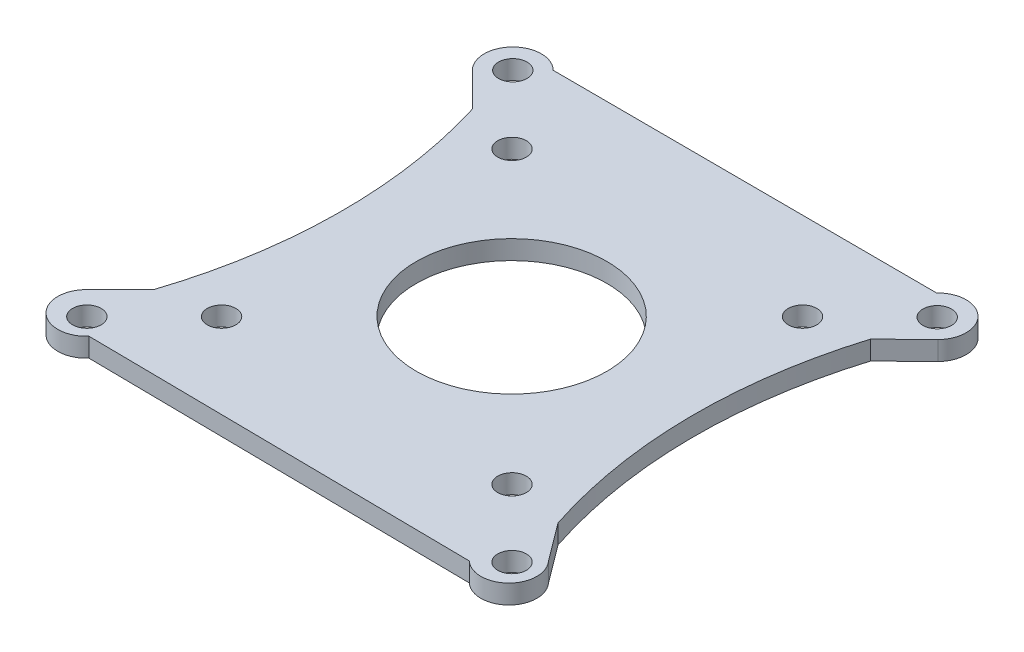
SolidWorks part; units mm, degrees
ref_plane "Front Plane" through (0, 0, 0) normal (0, 0, 1) x (1, 0, 0)
ref_plane "Top Plane" through (0, 0, 0) normal (0, 1, 0) x (1, 0, 0)
ref_plane "Right Plane" through (0, 0, 0) normal (1, 0, 0) x (0, 0, -1)
sketch "Sketch2" plane through (0, 0, 0) normal (0, 1, 0) x (1, 0, 0)
  line L0 (-78.5, 64.25) -> (-64.25, 78.5)
  line L1 (-15.25, 15.25) -> (15.25, 15.25)
  line L2 (-15.25, 15.25) -> (-15.25, -15.25)
  line L3 (-15.25, -15.25) -> (15.25, -15.25)
  line L4 (15.25, 15.25) -> (15.25, -15.25)
  line L5 (-15.25, 15.25) -> (15.25, -15.25) construction
  line L6 (-15.25, -15.25) -> (15.25, 15.25) construction
  line L7 (-78.5, 78.5) -> (78.5, 78.5)
  line L8 (-78.5, 78.5) -> (-78.5, -78.5)
  line L9 (-78.5, -78.5) -> (78.5, -78.5)
  line L10 (78.5, 78.5) -> (78.5, -78.5)
  line L11 (-78.5, 78.5) -> (78.5, -78.5) construction
  line L12 (-78.5, -78.5) -> (78.5, 78.5) construction
  line L13 (-78.5, 78.5) -> (-78.5457, 86.3999)
  line L19 (-78.5457, 64.1499) -> (-78.5457, 92.8503) construction
  line L21 (-78.5457, 86.3999) -> (-78.5457, 89.6265) construction
  line L22 (-79.8023, 86.3999) -> (-79.8023, 89.6265)
  line L23 (-77.2891, 86.3999) -> (-77.2891, 89.6265)
  line L24 (-78.5457, 70.6001) -> (-78.5457, 67.3735) construction
  line L25 (-79.8023, 70.6001) -> (-79.8023, 67.3735)
  line L26 (-77.2891, 70.6001) -> (-77.2891, 67.3735)
  line L27 (-70.6001, 78.5457) -> (-67.3735, 78.5457) construction
  line L28 (-70.6001, 79.8023) -> (-67.3735, 79.8023)
  line L29 (-70.6001, 77.2891) -> (-67.3735, 77.2891)
  line L30 (-86.3999, 78.4543) -> (-89.6263, 78.4169) construction
  line L31 (-86.4144, 79.7108) -> (-89.6408, 79.6734)
  line L32 (-86.3853, 77.1978) -> (-89.6117, 77.1604)
  line L33 (-78.5457, 89.6265) -> (-78.5457, 101.6265)
  line L34 (-89.6263, 78.4169) -> (-101.6263, 78.4169)
  line L37 (-98.95, 74.7808) -> (-96.0674, 74.0956)
  line L38 (-86.7416, 84.6885) -> (-82.0766, 89.227)
  line L41 (-67.3735, 78.5457) -> (-62.4, 78.5)
  line L42 (-78.5457, 67.3735) -> (-78.5, 62.4)
  line L45 (-86.682, 72.3894) -> (-84.5681, 70.2606)
  line L46 (-72.441, 86.7484) -> (-70.3091, 84.6014)
  line L52 (-78.5, 78.5) -> (-96.7698, 97.3427)
  line L54 (-74.7046, 101.5201) -> (-73.5555, 95.9231)
  line L56 (-95.0739, 82.9214) -> (-87.7318, 84.4523)
  line L57 (-80.7017, 101.7053) -> (-82.0766, 89.227)
  line L59 (0, 78.5) -> (0, 103.571)
  line L60 (78.5, 0) -> (99.7998, 0)
  line L61 (80.7017, 101.7053) -> (81.5231, 94.2504)
  line L62 (95.0739, 82.9214) -> (87.7318, 84.4523)
  line L63 (98.95, 74.7808) -> (96.0674, 74.0956)
  line L64 (61.5752, 75.5294) -> (74.7792, 62.5354)
  line L65 (74.7046, 101.5201) -> (73.5555, 95.9231)
  line L66 (78.5457, 70.6001) -> (78.5457, 67.3735) construction
  line L67 (79.8023, 70.6001) -> (79.8023, 67.3735)
  line L68 (77.2891, 70.6001) -> (77.2891, 67.3735)
  line L69 (70.6001, 78.5457) -> (67.3735, 78.5457) construction
  line L70 (70.6001, 79.8023) -> (67.3735, 79.8023)
  line L71 (70.6001, 77.2891) -> (67.3735, 77.2891)
  line L72 (86.3999, 78.4543) -> (89.6263, 78.4169) construction
  line L73 (86.4144, 79.7108) -> (89.6408, 79.6734)
  line L74 (86.3853, 77.1978) -> (89.6117, 77.1604)
  line L75 (78.5457, 86.3999) -> (78.5457, 89.6265) construction
  line L76 (79.8023, 86.3999) -> (79.8023, 89.6265)
  line L77 (77.2891, 86.3999) -> (77.2891, 89.6265)
  line L78 (74.7046, -101.5201) -> (73.5555, -95.9231)
  line L79 (61.5752, -75.5294) -> (74.7792, -62.5354)
  line L80 (98.95, -74.7808) -> (96.0674, -74.0956)
  line L81 (95.0739, -82.9214) -> (87.7318, -84.4523)
  line L82 (80.7017, -101.7053) -> (81.5231, -94.2504)
  line L83 (70.6001, -78.5457) -> (67.3735, -78.5457) construction
  line L84 (70.6001, -79.8023) -> (67.3735, -79.8023)
  line L85 (70.6001, -77.2891) -> (67.3735, -77.2891)
  line L86 (78.5457, -70.6001) -> (78.5457, -67.3735) construction
  line L87 (79.8023, -70.6001) -> (79.8023, -67.3735)
  line L88 (77.2891, -70.6001) -> (77.2891, -67.3735)
  line L89 (86.3999, -78.4543) -> (89.6263, -78.4169) construction
  line L90 (86.4144, -79.7108) -> (89.6408, -79.6734)
  line L91 (86.3853, -77.1978) -> (89.6117, -77.1604)
  line L92 (78.5457, -86.3999) -> (78.5457, -89.6265) construction
  line L93 (79.8023, -86.3999) -> (79.8023, -89.6265)
  line L94 (77.2891, -86.3999) -> (77.2891, -89.6265)
  line L95 (-80.7017, -101.7053) -> (-81.5231, -94.2504)
  line L96 (-95.0739, -82.9214) -> (-87.7318, -84.4523)
  line L97 (-98.95, -74.7808) -> (-96.0674, -74.0956)
  line L98 (-61.5752, -75.5294) -> (-74.7792, -62.5354)
  line L99 (-74.7046, -101.5201) -> (-73.5555, -95.9231)
  line L100 (-78.5457, -70.6001) -> (-78.5457, -67.3735) construction
  line L101 (-79.8023, -70.6001) -> (-79.8023, -67.3735)
  line L102 (-77.2891, -70.6001) -> (-77.2891, -67.3735)
  line L103 (-70.6001, -78.5457) -> (-67.3735, -78.5457) construction
  line L104 (-70.6001, -79.8023) -> (-67.3735, -79.8023)
  line L105 (-70.6001, -77.2891) -> (-67.3735, -77.2891)
  line L106 (-78.5457, -86.3999) -> (-78.5457, -89.6265) construction
  line L107 (-79.8023, -86.3999) -> (-79.8023, -89.6265)
  line L108 (-77.2891, -86.3999) -> (-77.2891, -89.6265)
  line L109 (-86.3999, -78.4543) -> (-89.6263, -78.4169) construction
  line L110 (-86.4144, -79.7108) -> (-89.6408, -79.6734)
  line L111 (-86.3853, -77.1978) -> (-89.6117, -77.1604)
  line L112 (-68.2471, 69.1034) -> (-15.25, 15.25)
  line L115 (-7.092, 0.0032) -> (-0.0457, 0.0032)
  line L116 (-57.359, 65.8476) -> (-0.0457, 6.9362)
  line L117 (-0.0457, 0.0032) -> (7.046, -0.045)
  line L120 (-65.1662, 58.1645) -> (-7.092, 0.0032)
  line L122 (-0.0457, 6.9362) -> (-0.0457, 0.0032)
  line L123 (-22.3211, 22.3211) -> (-22.3211, -22.3211)
  line L124 (58.074, 65.0536) -> (-0.0457, 6.9362)
  line L125 (65.1544, 58.0823) -> (7.046, -0.045)
  line L129 (-24.4854, 20.3204) -> (-20.9526, 16.7822)
  line L130 (-24.8039, -19.8891) -> (-21.2684, -16.3536)
  line L131 (20.8612, 16.7822) -> (24.4441, 20.2697)
  line L132 (21.1769, -16.3536) -> (24.1745, -20.3554)
  line L133 (-20.4308, -23.9927) -> (19.9775, -24.4602)
  line L134 (20.126, 24.4385) -> (-20.2399, 24.5601)
  line L135 (-22.3211, -22.3211) -> (22.3211, -22.3211)
  line L136 (22.3211, 22.3211) -> (22.3211, -22.3211)
  line L137 (-22.3211, 22.3211) -> (22.3211, 22.3211)
  circle A0 centre (-15.25, 15.25) radius 1.5
  circle A1 centre (15.25, 15.25) radius 1.5
  circle A2 centre (-15.25, -15.25) radius 1.5
  circle A3 centre (15.25, -15.25) radius 1.5
  circle A4 centre (-78.5, 78.5) radius 64.77
  circle A6 centre (78.5, -78.5) radius 64.77
  circle A7 centre (-78.5, -78.5) radius 64.77
  circle A9 centre (-78.5, 78.5) radius 14.25
  circle A12 centre (78.5, 78.5) radius 14.25
  arc A14 (-79.8023, 86.3999) -> (-77.2891, 86.3999) centre (-78.5457, 86.3999) ccw
  arc A15 (-77.2891, 89.6265) -> (-79.8023, 89.6265) centre (-78.5457, 89.6265) ccw
  arc A16 (-79.8023, 70.6001) -> (-77.2891, 70.6001) centre (-78.5457, 70.6001) cw
  arc A17 (-77.2891, 67.3735) -> (-79.8023, 67.3735) centre (-78.5457, 67.3735) cw
  circle A18 centre (-78.5, 78.5) radius 3
  arc A19 (-70.6001, 79.8023) -> (-70.6001, 77.2891) centre (-70.6001, 78.5457) ccw
  arc A20 (-67.3735, 77.2891) -> (-67.3735, 79.8023) centre (-67.3735, 78.5457) ccw
  arc A21 (-86.4144, 79.7108) -> (-86.3853, 77.1978) centre (-86.3999, 78.4543) cw
  arc A22 (-89.6117, 77.1604) -> (-89.6408, 79.6734) centre (-89.6263, 78.4169) cw
  arc A27 (-82.6259, 62.6487) -> (-74.7792, 62.5354) centre (-78.6792, 64.2065) ccw
  arc A28 (-62.5289, 82.1346) -> (-61.5752, 75.5294) centre (-64.6461, 78.4575) cw
  arc A29 (-96.0674, 74.0956) -> (-82.6259, 62.6487) centre (-108.6109, 45.7511) cw
  arc A30 (-73.5555, 95.9231) -> (-62.5289, 82.1346) centre (-44.8373, 107.5857) ccw
  arc A31 (-102.1815, 75.4688) -> (-102.1173, 81.3765) centre (-101.6263, 78.4169) cw
  arc A32 (-74.7046, 101.5201) -> (-80.7017, 101.7053) centre (-77.7031, 101.6127) ccw
  arc A33 (-102.1815, 75.4688) -> (-98.95, 74.7808) centre (-115.1374, 6.6782) cw
  arc A34 (-102.1173, 81.3765) -> (-95.0739, 82.9214) centre (-113.5733, 150.4327) ccw
  arc A35 (-87.7318, 84.4523) -> (-81.5231, 94.2504) centre (-96.6322, 96.9583) ccw
  arc A36 (87.7318, 84.4523) -> (81.5231, 94.2504) centre (96.6322, 96.9583) cw
  arc A37 (102.1173, 81.3765) -> (95.0739, 82.9214) centre (113.5733, 150.4327) cw
  arc A38 (102.1815, 75.4688) -> (102.1173, 81.3765) centre (101.6263, 78.4169) ccw
  arc A39 (102.1815, 75.4688) -> (98.95, 74.7808) centre (115.1374, 6.6782) ccw
  arc A40 (96.0674, 74.0956) -> (82.6259, 62.6487) centre (108.6109, 45.7511) ccw
  arc A41 (82.6259, 62.6487) -> (74.7792, 62.5354) centre (78.6792, 64.2065) cw
  arc A42 (62.5289, 82.1346) -> (61.5752, 75.5294) centre (64.6461, 78.4575) ccw
  arc A43 (73.5555, 95.9231) -> (62.5289, 82.1346) centre (44.8373, 107.5857) cw
  arc A44 (74.7046, 101.5201) -> (80.7017, 101.7053) centre (77.7031, 101.6127) cw
  arc A45 (79.8023, 70.6001) -> (77.2891, 70.6001) centre (78.5457, 70.6001) ccw
  arc A46 (77.2891, 67.3735) -> (79.8023, 67.3735) centre (78.5457, 67.3735) ccw
  arc A47 (70.6001, 79.8023) -> (70.6001, 77.2891) centre (70.6001, 78.5457) cw
  arc A48 (67.3735, 77.2891) -> (67.3735, 79.8023) centre (67.3735, 78.5457) cw
  arc A49 (86.4144, 79.7108) -> (86.3853, 77.1978) centre (86.3999, 78.4543) ccw
  arc A50 (89.6117, 77.1604) -> (89.6408, 79.6734) centre (89.6263, 78.4169) ccw
  arc A51 (79.8023, 86.3999) -> (77.2891, 86.3999) centre (78.5457, 86.3999) cw
  arc A52 (77.2891, 89.6265) -> (79.8023, 89.6265) centre (78.5457, 89.6265) cw
  circle A53 centre (78.5, 78.5) radius 3
  arc A54 (74.7046, -101.5201) -> (80.7017, -101.7053) centre (77.7031, -101.6127) ccw
  arc A55 (73.5555, -95.9231) -> (62.5289, -82.1346) centre (44.8373, -107.5857) ccw
  arc A56 (62.5289, -82.1346) -> (61.5752, -75.5294) centre (64.6461, -78.4575) cw
  arc A57 (82.6259, -62.6487) -> (74.7792, -62.5354) centre (78.6792, -64.2065) ccw
  arc A58 (96.0674, -74.0956) -> (82.6259, -62.6487) centre (108.6109, -45.7511) cw
  arc A59 (102.1815, -75.4688) -> (98.95, -74.7808) centre (115.1374, -6.6782) cw
  arc A60 (102.1815, -75.4688) -> (102.1173, -81.3765) centre (101.6263, -78.4169) cw
  arc A61 (102.1173, -81.3765) -> (95.0739, -82.9214) centre (113.5733, -150.4327) ccw
  arc A62 (87.7318, -84.4523) -> (81.5231, -94.2504) centre (96.6322, -96.9583) ccw
  arc A63 (70.6001, -79.8023) -> (70.6001, -77.2891) centre (70.6001, -78.5457) ccw
  arc A64 (67.3735, -77.2891) -> (67.3735, -79.8023) centre (67.3735, -78.5457) ccw
  arc A65 (79.8023, -70.6001) -> (77.2891, -70.6001) centre (78.5457, -70.6001) cw
  arc A66 (77.2891, -67.3735) -> (79.8023, -67.3735) centre (78.5457, -67.3735) cw
  arc A67 (86.4144, -79.7108) -> (86.3853, -77.1978) centre (86.3999, -78.4543) cw
  arc A68 (89.6117, -77.1604) -> (89.6408, -79.6734) centre (89.6263, -78.4169) cw
  arc A69 (79.8023, -86.3999) -> (77.2891, -86.3999) centre (78.5457, -86.3999) ccw
  arc A70 (77.2891, -89.6265) -> (79.8023, -89.6265) centre (78.5457, -89.6265) ccw
  circle A71 centre (78.5, -78.5) radius 3
  circle A72 centre (78.5, -78.5) radius 14.25
  arc A73 (-87.7318, -84.4523) -> (-81.5231, -94.2504) centre (-96.6322, -96.9583) cw
  arc A74 (-102.1173, -81.3765) -> (-95.0739, -82.9214) centre (-113.5733, -150.4327) cw
  arc A75 (-102.1815, -75.4688) -> (-102.1173, -81.3765) centre (-101.6263, -78.4169) ccw
  arc A76 (-102.1815, -75.4688) -> (-98.95, -74.7808) centre (-115.1374, -6.6782) ccw
  arc A77 (-96.0674, -74.0956) -> (-82.6259, -62.6487) centre (-108.6109, -45.7511) ccw
  arc A78 (-82.6259, -62.6487) -> (-74.7792, -62.5354) centre (-78.6792, -64.2065) cw
  arc A79 (-62.5289, -82.1346) -> (-61.5752, -75.5294) centre (-64.6461, -78.4575) ccw
  arc A80 (-73.5555, -95.9231) -> (-62.5289, -82.1346) centre (-44.8373, -107.5857) cw
  arc A81 (-74.7046, -101.5201) -> (-80.7017, -101.7053) centre (-77.7031, -101.6127) cw
  circle A82 centre (-78.5, -78.5) radius 14.25
  circle A83 centre (-78.5, -78.5) radius 3
  arc A84 (-79.8023, -70.6001) -> (-77.2891, -70.6001) centre (-78.5457, -70.6001) ccw
  arc A85 (-77.2891, -67.3735) -> (-79.8023, -67.3735) centre (-78.5457, -67.3735) ccw
  arc A86 (-70.6001, -79.8023) -> (-70.6001, -77.2891) centre (-70.6001, -78.5457) cw
  arc A87 (-67.3735, -77.2891) -> (-67.3735, -79.8023) centre (-67.3735, -78.5457) cw
  arc A88 (-79.8023, -86.3999) -> (-77.2891, -86.3999) centre (-78.5457, -86.3999) cw
  arc A89 (-77.2891, -89.6265) -> (-79.8023, -89.6265) centre (-78.5457, -89.6265) cw
  arc A90 (-86.4144, -79.7108) -> (-86.3853, -77.1978) centre (-86.3999, -78.4543) ccw
  arc A91 (-89.6117, -77.1604) -> (-89.6408, -79.6734) centre (-89.6263, -78.4169) ccw
  arc A92 (-74.7792, 62.5354) -> (-65.1662, 58.1645) centre (-77.9098, 42.8938) cw
  arc A93 (-61.5752, 75.5294) -> (-57.359, 65.8476) centre (-41.8859, 78.3448) ccw
  arc A95 (74.7792, 62.5354) -> (65.1544, 58.0823) centre (78.0173, 42.9089) ccw
  arc A96 (61.5752, 75.5294) -> (58.074, 65.0536) centre (41.7003, 76.349) cw
  circle A97 centre (78.5, 78.5) radius 64.77
  arc A113 (-20.4308, -23.9927) -> (-24.8039, -19.8891) centre (-22.6826, -22.0104) cw
  arc A114 (-20.2399, 24.5601) -> (-24.4854, 20.3204) centre (-22.3625, 22.4401) ccw
  arc A115 (19.9775, -24.4602) -> (24.1745, -20.3554) centre (21.9877, -22.3175) ccw
  arc A116 (20.126, 24.4385) -> (24.4441, 20.2697) centre (22.3052, 22.3749) cw
  arc A117 (-20.9526, 16.7822) -> (-21.2684, -16.3536) centre (-73.303, 0.7117) cw
  arc A118 (20.8612, 16.7822) -> (21.1769, -16.3536) centre (73.2116, 0.7117) ccw
  circle A119 centre (-0.0457, 0.0032) radius 10
  circle A120 centre (22.372, 22.2698) radius 1.5
  circle A121 centre (22.3211, -22.3211) radius 1.5
  circle A122 centre (-22.3211, -22.3211) radius 1.5
  circle A123 centre (-22.3625, 22.4401) radius 1.5
  point P0 (0, 0)
  point P10 (0, 0)
  point P29 (-78.5457, 88.0132)
  point P38 (-78.5457, 68.9868)
  point P46 (-68.9868, 78.5457)
  point P53 (-88.0131, 78.4356)
  point P67 (-101.6263, 78.4169)
  point P70 (-78.5457, 101.6265)
  point P75 (-84.4091, 86.9578)
  point P82 (-78.5, 62.4)
  point P85 (-62.4, 78.5)
  point P86 (-62.4, 78.5)
  point P91 (-85.625, 71.325)
  point P94 (-71.3751, 85.6749)
  point P99 (-101.6263, 75.4169)
  point P102 (-101.6263, 81.4169)
  point P135 (78.5457, 68.9868)
  point P142 (68.9868, 78.5457)
  point P149 (88.0131, 78.4356)
  point P156 (78.5457, 88.0132)
  point P187 (68.9868, -78.5457)
  point P194 (78.5457, -68.9868)
  point P201 (88.0131, -78.4356)
  point P208 (78.5457, -88.0132)
  point P242 (-78.5457, -68.9868)
  point P249 (-68.9868, -78.5457)
  point P256 (-78.5457, -88.0132)
  point P263 (-88.0131, -78.4356)
  point P292 (-22.5658, -22.0676)
  point P296 (-22.2642, 22.3775)
  point P300 (22.0677, -22.5656)
  point P304 (22.372, 22.2698)
  dimension "D3" = 157
  dimension "D5" = 7.9
  dimension "D6" = 12
  dimension "D8" = 6
  dimension "D9" = 70
  dimension "D12" = 70
  dimension "D19" = 5
  dimension "D1" = 30.5
  dimension "D2" = 30.5
  dimension "D4" = 157
  dimension "D7" = 12
  dimension "D10" = 3
  dimension "D11" = 3
  dimension "D13" = 7.5
  dimension "D14" = 7.5
  dimension "D17" = 5
  dimension "D15" = 82.191
  dimension "D16" = 82.191
  dimension "D18" = 7.0711
  dimension "D20" = 5
  dimension "D21" = 5
extrude "Boss-Extrude2" add sketch "Sketch2" along normal blind 2 contours A122 L135 A121 L136 L132 A118 L125 L4 A3 L3 A2 L2 L120 A117 L130 L123 | A122 L123 L130 A113 L133 A115 L132 L136 A121 L135 | A119 L120 L2 A2 L3 A3 L4 L125 | A119 L125 L4 A1 L1 L124 | A119 L124 L1 L116 | A119 L116 L1 A0 L2 L120 | A120 L137 L124 L1 A1 L4 L125 A118 L131 L136 | L137 L116 L1 L124 | A120 L136 L131 A116 L134 L124 L137 | L116 L137 L124 L134 | A123 L137 L116 L134 A114 L112 | A123 L112 A114 L129 L123 | A123 L123 L129 A117 L120 L2 A0 L112 | A123 L112 A0 L1 L116 L137 region at (-19.7354, 0, -23.7345) region at (-23.9111, 0, -21.453) region at (0.0308, 0, -23.4341) region at (-18.5666, 0, -15.1397) region at (-17.9766, 0, -10.0999) region at (-0.3375, 0, 22.9804) region at (0.12, 0, -19.1372) region at (-15.0787, 0, -18.903) region at (18.7952, 0, -24.3197) region at (-12.7466, 0, -5.122) region at (-10.1356, 0, -10.1226) region at (0.0374, 0, -12.9893) region at (16.757, 0, -17.102) region at (10.1305, 0, -10.0801)
